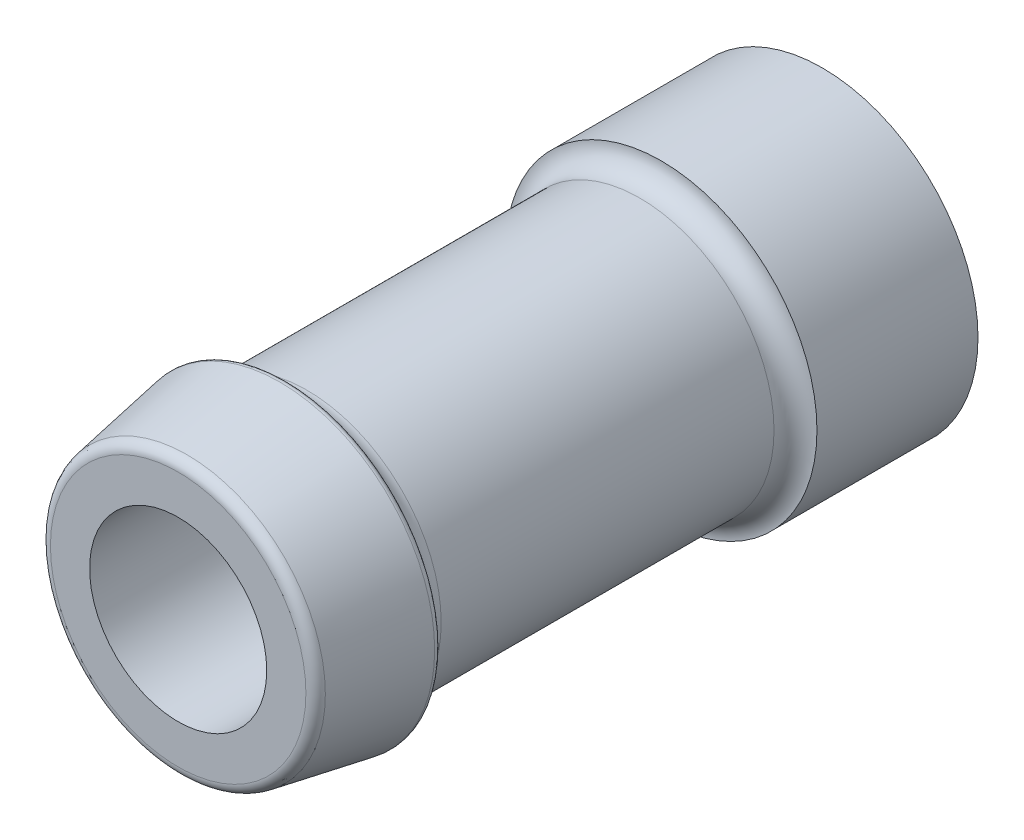
SolidWorks part; units mm, degrees
material "Custom Plastic"
ref_plane "X-Y Datum" through (0, 0, 0) normal (0, 0, 1) x (1, 0, 0)
ref_plane "X-Z Datum" through (0, 0, 0) normal (0, 1, 0) x (1, 0, 0)
ref_plane "Y-Z Datum" through (0, 0, 0) normal (1, 0, 0) x (0, 0, -1)
sketch "Sketch1" plane through (0, 0, 0) normal (0, 0, 1) x (1, 0, 0)
  circle A0 centre (0, 0) radius 7.366
  dimension "D1" = 14.732
extrude "Boss-Extrude1" add sketch "Sketch1" along normal blind 30.48
sketch "Sketch2" plane through (0, 0, 30.48) normal (0, 0, 1) x (1, 0, 0)
  circle A0 centre (0, 0) radius 4.191
  dimension "D1" = 8.382
extrude "Cut-Extrude1" cut sketch "Sketch2" against normal blind 30.48
sketch "Sketch3" plane through (0, 0, 30.48) normal (0, 0, 1) x (1, 0, 0)
  circle A0 centre (0, 0) radius 6.35
  circle A1 centre (0, 0) radius 10.16
  dimension "D1" = 12.7
  dimension "D2" = 20.32
extrude "Cut-Extrude2" cut sketch "Sketch3" against normal blind 17.78 from offset 5.08 offset against normal yes
fillet "Fillet1" radius 1.016 1 edges at (6.35, 0, 7.62)
fillet "Fillet2" radius 1.016 1 edges at (6.35, 0, 25.4)
chamfer "Chamfer1" distance 5.08 angle 10 1 edges at (7.366, 0, 30.48) first distance on face at (7.366, 0, 25.4)
fillet "Fillet3" radius 0.508 1 edges at (6.4703, 0, 30.48)
fillet "Fillet4" radius 0.254 1 edges at (7.366, 0, 25.4)
